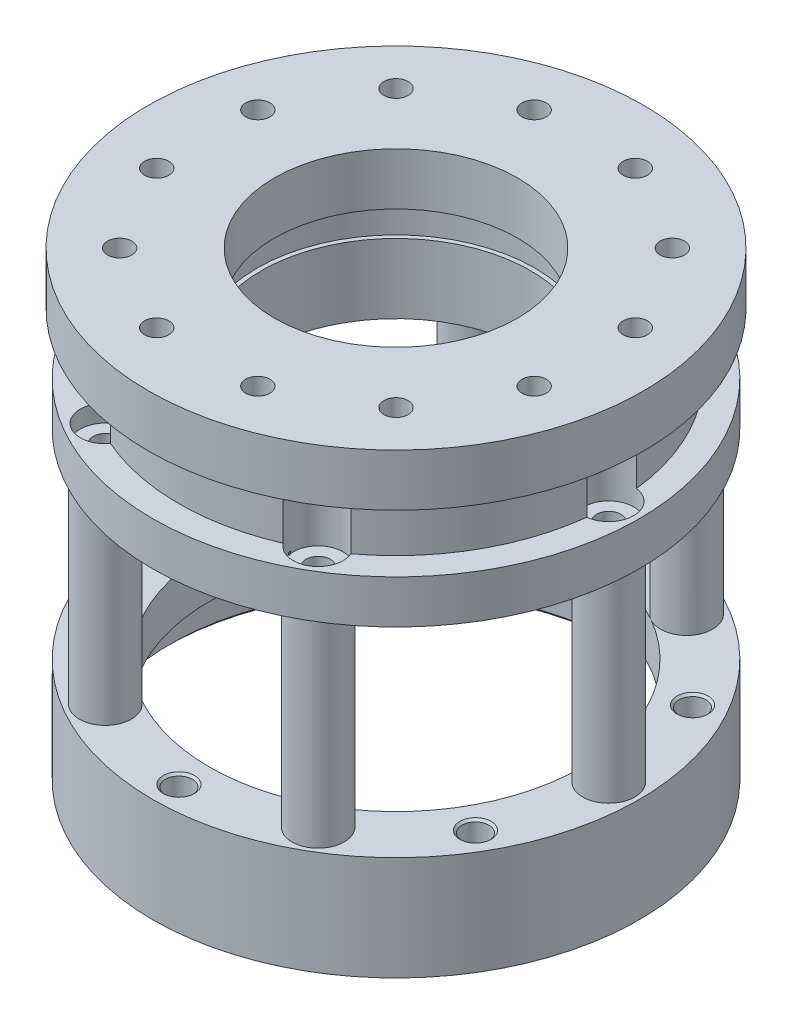
SolidWorks part; units mm, degrees
ref_plane "Front" through (0, 0, 0) normal (0, 0, 1) x (1, 0, 0)
ref_plane "Top" through (0, 0, 0) normal (0, 1, 0) x (1, 0, 0)
ref_plane "Right" through (0, 0, 0) normal (1, 0, 0) x (0, 0, -1)
sketch "Sketch1" plane through (0, 0, 0) normal (0, 1, 0) x (1, 0, 0)
  line L0 (0, 0) -> (24.5, 0) construction
  circle A0 centre (24.5, 0) radius 3
  dimension "D2" = 6
  dimension "D1" = 24.5
extrude "Boss-Extrude1" add sketch "Sketch1" along normal blind 23
ref_axis "Axis1" through (0, -50, 0) along (0, 1, 0)
pattern_circular "CirPattern1" count 6 over 360 about axis through (0, -50, 0) along (0, 1, 0) of "Boss-Extrude1"
sketch "Sketch3" plane through (0, 0, 0) normal (0, 1, 0) x (1, 0, 0)
  circle A0 centre (0, 0) radius 28
  circle A1 centre (0, 0) radius 21.5
  dimension "D1" = 56
  dimension "D2" = 43
extrude "Boss-Extrude2" add sketch "Sketch3" against normal blind 5
sketch "Sketch4" plane through (0, -5, 0) normal (0, -1, 0) x (1, 0, 0)
  circle A0 centre (0, 0) radius 26
  circle A1 centre (0, 0) radius 28 construction
  circle A2 centre (0, 0) radius 28
  dimension "D1" = 52
extrude "Boss-Extrude3" add sketch "Sketch4" along normal blind 7
sketch "Sketch5" plane through (0, 0, 0) normal (0, 1, 0) x (1, 0, 0)
  line L0 (0, 0) -> (21.5, 0) construction
  line L1 (0, 0) -> (21.6506, -12.5) construction
  circle A0 centre (0, 0) radius 21.5 construction
  circle A1 centre (21.6506, -12.5) radius 1.55
  circle A2 centre (0, -25) radius 1.55
  circle A3 centre (-21.6506, -12.5) radius 1.55
  circle A4 centre (-21.6506, 12.5) radius 1.55
  circle A5 centre (0, 25) radius 1.55
  circle A6 centre (21.6506, 12.5) radius 1.55
  dimension "D3" = 3.1
  dimension "D1" = 25
  dimension "D2" = 30
  dimension "D4" = 6
extrude "Cut-Extrude1" cut sketch "Sketch5" against normal blind 4
chamfer "Chamfer1" distance 0.25 angle 45 6 edges at (0, 0, -23.45) (-21.6506, 0, -10.95) (-21.6506, 0, 14.05) (0, 0, 26.55) (21.6506, 0, 14.05) (21.6506, 0, -10.95)
sketch "Sketch6" plane through (0, 23, 0) normal (0, 1, 0) x (1, 0, 0)
  circle A0 centre (0, 0) radius 28
  circle A1 centre (0, 0) radius 15.5
  dimension "D1" = 56
  dimension "D2" = 31
extrude "Boss-Extrude4" add sketch "Sketch6" along normal blind 5 separate body
sketch "Sketch7" plane through (0, 28, 0) normal (0, 1, 0) x (1, 0, 0)
  circle A0 centre (0, 0) radius 25
  circle A1 centre (0, 0) radius 15.5 construction
  circle A2 centre (0, 0) radius 15.5
  dimension "D1" = 50
extrude "Boss-Extrude5" add sketch "Sketch7" along normal blind 7
sketch "Sketch8" plane through (0, 35, 0) normal (0, 1, 0) x (1, 0, 0)
  circle A0 centre (0, 0) radius 16
  dimension "D1" = 32
extrude "Cut-Extrude2" cut sketch "Sketch8" against normal blind 4
sketch "Sketch9" plane through (0, 23, 0) normal (0, -1, 0) x (1, 0, 0)
  circle A0 centre (21.6506, 12.5) radius 1.55 construction
  circle A1 centre (21.6506, 12.5) radius 1.55
extrude "Cut-Extrude3" cut sketch "Sketch9" against normal blind 4.5
chamfer "Chamfer2" distance 0.25 angle 45 1 edges at (21.6506, 23, 10.95)
pattern_circular "CirPattern2" count 6 over 360 about axis through (0, 35, 0) along (0, -1, 0) of "Chamfer2", "Cut-Extrude3"
sketch "Sketch10" plane through (0, 35, 0) normal (0, 1, 0) x (1, 0, 0)
  circle A0 centre (0, 0) radius 28.5
  circle A1 centre (0, 0) radius 14
  dimension "D1" = 57
  dimension "D2" = 28
extrude "Boss-Extrude6" add sketch "Sketch10" along normal blind 6 separate body
sketch "Sketch11" plane through (0, 28, 0) normal (0, 1, 0) x (1, 0, 0)
  circle A0 centre (24.5, 0) radius 2.875
  dimension "D1" = 5.75
extrude "Cut-Extrude4" cut sketch "Sketch11" against normal blind 2 and the other way up to surface (7 mm away) other way up to face at (0, 35, 28.5)
sketch "Sketch12" plane through (0, 26, 0) normal (0, 1, 0) x (1, 0, 0)
  circle A0 centre (24.5, 0) radius 1.4
  dimension "D1" = 2.8
extrude "Cut-Extrude5" cut sketch "Sketch12" against normal blind 28
pattern_circular "CirPattern3" count 6 over 360 about axis through (0, 35, 0) along (0, -1, 0) of "Cut-Extrude4", "Cut-Extrude5" reverse direction yes
chamfer "Chamfer3" distance 0.5 angle 45 1 edges at (0, -12, -26)
sketch "Sketch13" plane through (0, 41, 0) normal (0, 1, 0) x (1, 0, 0)
  line L0 (0, 0) -> (18.4774, 0) construction
  line L1 (0, 0) -> (21.7333, -5.8234) construction
  circle A1 centre (0, 0) radius 16 construction
  circle A2 centre (0, 0) radius 16 construction
  arc A3 (14.8909, -20.0813) -> (24.8364, -2.8552) centre (0, 0) ccw construction
  arc A4 (14.8909, -20.0813) -> (24.8364, -2.8552) centre (0, 0) ccw construction
  circle A5 centre (21.7333, -5.8234) radius 1.4
  circle A6 centre (15.9099, -15.9099) radius 1.4
  circle A7 centre (5.8234, -21.7333) radius 1.4
  circle A8 centre (-5.8234, -21.7333) radius 1.4
  circle A9 centre (-15.9099, -15.9099) radius 1.4
  circle A10 centre (-21.7333, -5.8234) radius 1.4
  circle A11 centre (-21.7333, 5.8234) radius 1.4
  circle A12 centre (-15.9099, 15.9099) radius 1.4
  circle A13 centre (-5.8234, 21.7333) radius 1.4
  circle A14 centre (5.8234, 21.7333) radius 1.4
  circle A15 centre (15.9099, 15.9099) radius 1.4
  circle A16 centre (21.7333, 5.8234) radius 1.4
  dimension "D1" = 2.8
  dimension "D2" = 15
  dimension "D3" = 22.5
  dimension "D4" = 12
extrude "Cut-Extrude6" cut sketch "Sketch13" against normal blind 16
sketch "Sketch14" plane through (0, 23, 0) normal (0, -1, 0) x (1, 0, 0)
  line L0 (0, 0) -> (8.5317, 0) construction
  line L1 (0, 0) -> (21.7333, 5.8234) construction
  line L2 (24.9083, -7.6565) -> (24.9083, -3.9903)
  line L3 (25.3995, 5.8234) -> (23.5664, 8.9984)
  line L4 (23.5664, 8.9984) -> (19.9002, 8.9984)
  line L5 (19.9002, 8.9984) -> (18.0672, 5.8234)
  line L6 (18.0672, 5.8234) -> (19.9002, 2.6484)
  line L7 (19.9002, 2.6484) -> (23.5664, 2.6484)
  line L8 (23.5664, 2.6484) -> (25.3995, 5.8234)
  line L9 (24.9083, -3.9903) -> (21.7333, -2.1573)
  line L10 (21.7333, -2.1573) -> (18.5583, -3.9903)
  line L11 (18.5583, -3.9903) -> (18.5583, -7.6565)
  line L12 (18.5583, -7.6565) -> (21.7333, -9.4896)
  line L13 (21.7333, -9.4896) -> (24.9083, -7.6565)
  line L14 (17.743, -19.0849) -> (19.5761, -15.9099)
  line L15 (19.5761, -15.9099) -> (17.743, -12.7349)
  line L16 (17.743, -12.7349) -> (14.0768, -12.7349)
  line L17 (14.0768, -12.7349) -> (12.2437, -15.9099)
  line L18 (12.2437, -15.9099) -> (14.0768, -19.0849)
  line L19 (14.0768, -19.0849) -> (17.743, -19.0849)
  line L20 (5.8234, -25.3995) -> (8.9984, -23.5664)
  line L21 (8.9984, -23.5664) -> (8.9984, -19.9002)
  line L22 (8.9984, -19.9002) -> (5.8234, -18.0672)
  line L23 (5.8234, -18.0672) -> (2.6484, -19.9002)
  line L24 (2.6484, -19.9002) -> (2.6484, -23.5664)
  line L25 (2.6484, -23.5664) -> (5.8234, -25.3995)
  line L26 (-7.6565, -24.9083) -> (-3.9903, -24.9083)
  line L27 (-3.9903, -24.9083) -> (-2.1573, -21.7333)
  line L28 (-2.1573, -21.7333) -> (-3.9903, -18.5583)
  line L29 (-3.9903, -18.5583) -> (-7.6565, -18.5583)
  line L30 (-7.6565, -18.5583) -> (-9.4896, -21.7333)
  line L31 (-9.4896, -21.7333) -> (-7.6565, -24.9083)
  line L32 (-19.0849, -17.743) -> (-15.9099, -19.5761)
  line L33 (-15.9099, -19.5761) -> (-12.7349, -17.743)
  line L34 (-12.7349, -17.743) -> (-12.7349, -14.0768)
  line L35 (-12.7349, -14.0768) -> (-15.9099, -12.2437)
  line L36 (-15.9099, -12.2437) -> (-19.0849, -14.0768)
  line L37 (-19.0849, -14.0768) -> (-19.0849, -17.743)
  line L38 (-25.3995, -5.8234) -> (-23.5664, -8.9984)
  line L39 (-23.5664, -8.9984) -> (-19.9002, -8.9984)
  line L40 (-19.9002, -8.9984) -> (-18.0672, -5.8234)
  line L41 (-18.0672, -5.8234) -> (-19.9002, -2.6484)
  line L42 (-19.9002, -2.6484) -> (-23.5664, -2.6484)
  line L43 (-23.5664, -2.6484) -> (-25.3995, -5.8234)
  line L44 (-24.9083, 7.6565) -> (-24.9083, 3.9903)
  line L45 (-24.9083, 3.9903) -> (-21.7333, 2.1573)
  line L46 (-21.7333, 2.1573) -> (-18.5583, 3.9903)
  line L47 (-18.5583, 3.9903) -> (-18.5583, 7.6565)
  line L48 (-18.5583, 7.6565) -> (-21.7333, 9.4896)
  line L49 (-21.7333, 9.4896) -> (-24.9083, 7.6565)
  line L50 (-17.743, 19.0849) -> (-19.5761, 15.9099)
  line L51 (-19.5761, 15.9099) -> (-17.743, 12.7349)
  line L52 (-17.743, 12.7349) -> (-14.0768, 12.7349)
  line L53 (-14.0768, 12.7349) -> (-12.2437, 15.9099)
  line L54 (-12.2437, 15.9099) -> (-14.0768, 19.0849)
  line L55 (-14.0768, 19.0849) -> (-17.743, 19.0849)
  line L56 (-5.8234, 25.3995) -> (-8.9984, 23.5664)
  line L57 (-8.9984, 23.5664) -> (-8.9984, 19.9002)
  line L58 (-8.9984, 19.9002) -> (-5.8234, 18.0672)
  line L59 (-5.8234, 18.0672) -> (-2.6484, 19.9002)
  line L60 (-2.6484, 19.9002) -> (-2.6484, 23.5664)
  line L61 (-2.6484, 23.5664) -> (-5.8234, 25.3995)
  line L62 (7.6565, 24.9083) -> (3.9903, 24.9083)
  line L63 (3.9903, 24.9083) -> (2.1573, 21.7333)
  line L64 (2.1573, 21.7333) -> (3.9903, 18.5583)
  line L65 (3.9903, 18.5583) -> (7.6565, 18.5583)
  line L66 (7.6565, 18.5583) -> (9.4896, 21.7333)
  line L67 (9.4896, 21.7333) -> (7.6565, 24.9083)
  line L68 (19.0849, 17.743) -> (15.9099, 19.5761)
  line L69 (15.9099, 19.5761) -> (12.7349, 17.743)
  line L70 (12.7349, 17.743) -> (12.7349, 14.0768)
  line L71 (12.7349, 14.0768) -> (15.9099, 12.2437)
  line L72 (15.9099, 12.2437) -> (19.0849, 14.0768)
  line L73 (19.0849, 14.0768) -> (19.0849, 17.743)
  circle A0 centre (21.7333, 5.8234) radius 3.175 construction
  circle A1 centre (21.7333, -5.8234) radius 3.175 construction
  circle A2 centre (15.9099, -15.9099) radius 3.175 construction
  circle A3 centre (5.8234, -21.7333) radius 3.175 construction
  circle A4 centre (-5.8234, -21.7333) radius 3.175 construction
  circle A5 centre (-15.9099, -15.9099) radius 3.175 construction
  circle A6 centre (-21.7333, -5.8234) radius 3.175 construction
  circle A7 centre (-21.7333, 5.8234) radius 3.175 construction
  circle A8 centre (-15.9099, 15.9099) radius 3.175 construction
  circle A9 centre (-5.8234, 21.7333) radius 3.175 construction
  circle A10 centre (5.8234, 21.7333) radius 3.175 construction
  circle A11 centre (15.9099, 15.9099) radius 3.175 construction
  dimension "D1" = 15
  dimension "D2" = 22.5
  dimension "D3" = 6.35
  dimension "D4" = 12
extrude "Cut-Extrude7" cut sketch "Sketch14" against normal blind 3.25
chamfer "Chamfer4" distance 0.5 angle 45 7 edges at (0, 35, 16) (0, 35, 25) (21.6506, 35, 12.5) (21.6506, 35, -12.5) (0, 35, -25) (-21.6506, 35, -12.5) (-21.6506, 35, 12.5)
sketch "Sketch15" [suppressed] plane through (0, 41, 0) normal (0, 1, 0) x (1, 0, 0)
  line L0 (0, 0) -> (200, 0) construction
  line L1 (2.3571, 28.4024) -> (200, 12)
  line L2 (200, -12) -> (2.3571, -28.4024)
  circle A0 centre (0, 0) radius 17.3405
  arc A1 (2.3571, 28.4024) -> (2.3571, -28.4024) centre (0, 0) ccw
  arc A2 (200, -12) -> (200, 12) centre (200, 0) ccw
  circle A3 centre (0, 0) radius 28.5 construction
  dimension "D1" = 200
  dimension "D2" = 24
extrude "Boss-Extrude7" [suppressed] add sketch "Sketch15" along normal blind 6 separate body
sketch "Sketch16" [suppressed] plane through (0, 47, 0) normal (0, 1, 0) x (1, 0, 0)
  circle A0 centre (200, 0) radius 6
  dimension "D1" = 12
extrude "Boss-Extrude8" [suppressed] add sketch "Sketch16" along normal blind 14
sketch "Sketch17" [suppressed] plane through (0, 61, 0) normal (0, 1, 0) x (1, 0, 0)
  circle A0 centre (200, 0) radius 10
  dimension "D1" = 20
extrude "Boss-Extrude9" [suppressed] add sketch "Sketch17" along normal blind 4
sketch "Sketch18" [suppressed] plane through (0, 47, 0) normal (0, 1, 0) x (1, 0, 0)
  circle A0 centre (52.1814, 0) radius 14.0548
  circle A1 centre (88.1102, 0) radius 8.9972
  circle A2 centre (119.7664, 0) radius 7.2286
  circle A3 centre (149.4804, 0) radius 5.4975
extrude "Cut-Extrude8" [suppressed] cut sketch "Sketch18" against normal through all
sketch "Sketch20" [suppressed] plane through (0, 47, 0) normal (0, 1, 0) x (1, 0, 0)
  circle A0 centre (21.7333, 5.8234) radius 1.4 construction
  circle A1 centre (21.7333, -5.8234) radius 1.4 construction
  circle A2 centre (21.7333, 5.8234) radius 1.4
  circle A3 centre (21.7333, -5.8234) radius 1.4
  circle A4 centre (15.9099, -15.9099) radius 1.4 construction
  circle A5 centre (5.8234, -21.7333) radius 1.4 construction
  circle A6 centre (-5.8234, -21.7333) radius 1.4 construction
  circle A7 centre (-15.9099, -15.9099) radius 1.4 construction
  circle A8 centre (-21.7333, -5.8234) radius 1.4 construction
  circle A9 centre (-21.7333, 5.8234) radius 1.4 construction
  circle A10 centre (-15.9099, 15.9099) radius 1.4 construction
  circle A11 centre (-5.8234, 21.7333) radius 1.4 construction
  circle A12 centre (5.8234, 21.7333) radius 1.4 construction
  circle A13 centre (15.9099, 15.9099) radius 1.4 construction
  circle A14 centre (15.9099, -15.9099) radius 1.4
  circle A15 centre (5.8234, -21.7333) radius 1.4
  circle A16 centre (-5.8234, -21.7333) radius 1.4
  circle A17 centre (-15.9099, -15.9099) radius 1.4
  circle A18 centre (-21.7333, -5.8234) radius 1.4
  circle A19 centre (-21.7333, 5.8234) radius 1.4
  circle A20 centre (-15.9099, 15.9099) radius 1.4
  circle A21 centre (-5.8234, 21.7333) radius 1.4
  circle A22 centre (5.8234, 21.7333) radius 1.4
  circle A23 centre (15.9099, 15.9099) radius 1.4
extrude "Cut-Extrude9" [suppressed] cut sketch "Sketch20" against normal up to surface (6 mm away) up to face at (21.7333, 41, 7.2234)
sketch "Sketch21" [suppressed] plane through (0, 35, 0) normal (0, -1, 0) x (1, 0, 0)
  circle A0 centre (0, 0) radius 16
  dimension "D1" = 32
extrude "Cut-Extrude10" [suppressed] cut sketch "Sketch21" against normal blind 1
sketch "Sketch22" [suppressed] plane through (0, -4, 0) normal (0, 1, 0) x (1, 0, 0)
  circle A1 centre (21.6506, -12.5) radius 1.55
  circle A2 centre (21.6506, -12.5) radius 1.55
  dimension "D1" = 0
extrude "Boss-Extrude10" [suppressed] add sketch "Sketch22" along normal up to surface (31.5 mm away) separate body up to face at (21.6506, 27.5, 10.95)
pattern_circular "CirPattern5" [suppressed] count 6 over 360 reverse direction yes of bodies 133
sketch "Sketch23" [suppressed] plane through (0, 23, 0) normal (0, 1, 0) x (1, 0, 0)
  circle A0 centre (12.25, -21.2176) radius 1.4 construction
  circle A1 centre (12.25, -21.2176) radius 3
  circle A2 centre (12.25, -21.2176) radius 3
  circle A3 centre (12.25, -21.2176) radius 1.4
  dimension "D1" = 0
extrude "Boss-Extrude11" [suppressed] add sketch "Sketch23" along normal blind 2 separate body
sketch "Sketch24" [suppressed] plane through (0, 41, 0) normal (0, 1, 0) x (1, 0, 0)
  line L0 (0, 0) -> (200, 0) construction
  line L1 (3.0625, 34.8658) -> (201.5313, 17.4329)
  line L2 (3.0625, -34.8658) -> (201.5313, -17.4329)
  circle A4 centre (0, 0) radius 14 construction
  circle A5 centre (0, 0) radius 14
  arc A6 (3.0625, 34.8658) -> (3.0625, -34.8658) centre (0, 0) ccw
  arc A7 (201.5313, -17.4329) -> (201.5313, 17.4329) centre (200, 0) ccw
  arc A8 (35, 0) -> (3.0625, 34.8658) centre (0, 0) ccw construction
  arc A9 (3.0625, -34.8658) -> (35, 0) centre (0, 0) ccw construction
  arc A10 (182.5, 0) -> (201.5313, -17.4329) centre (200, 0) ccw construction
  arc A11 (201.5313, 17.4329) -> (182.5, 0) centre (200, 0) ccw construction
  dimension "D2" = 70
  dimension "D3" = 35
  dimension "D1" = 200
extrude "Boss-Extrude12" [suppressed] add sketch "Sketch24" along normal blind 20 separate body
sketch "Sketch25" [suppressed] plane through (0, 61, 0) normal (0, 1, 0) x (1, 0, 0)
  line L0 (0, 0) -> (200, 0) construction
  line L1 (200, 0) -> (210, 0) construction
  circle A0 centre (59.8852, 0) radius 20.3471
  circle A1 centre (116.238, 0) radius 16.1539
  circle A2 centre (164.0017, 0) radius 10.0532
  circle A3 centre (210, 0) radius 1.4
  circle A4 centre (203.0902, -9.5106) radius 1.4
  circle A5 centre (191.9098, -5.8779) radius 1.4
  circle A6 centre (191.9098, 5.8779) radius 1.4
  circle A7 centre (203.0902, 9.5106) radius 1.4
  dimension "D3" = 2.8
  dimension "D1" = 200
  dimension "D2" = 10
  dimension "D4" = 5
extrude "Cut-Extrude11" [suppressed] cut sketch "Sketch25" against normal up to surface (20 mm away) up to face at (21.7333, 41, 7.2234)
sketch "Sketch27" [suppressed] plane through (0, 61, 0) normal (0, 1, 0) x (1, 0, 0)
  circle A3 centre (21.7333, 5.8234) radius 1.4
  circle A4 centre (21.7333, 5.8234) radius 1.4
  circle A5 centre (15.9099, 15.9099) radius 1.4
  circle A6 centre (15.9099, 15.9099) radius 1.4
  circle A7 centre (5.8234, 21.7333) radius 1.4
  circle A8 centre (5.8234, 21.7333) radius 1.4
  circle A9 centre (-5.8234, 21.7333) radius 1.4
  circle A10 centre (-5.8234, 21.7333) radius 1.4
  circle A11 centre (-15.9099, 15.9099) radius 1.4
  circle A12 centre (-15.9099, 15.9099) radius 1.4
  circle A13 centre (-21.7333, 5.8234) radius 1.4
  circle A14 centre (-21.7333, 5.8234) radius 1.4
  circle A15 centre (-21.7333, -5.8234) radius 1.4
  circle A16 centre (-21.7333, -5.8234) radius 1.4
  circle A17 centre (-15.9099, -15.9099) radius 1.4
  circle A18 centre (-15.9099, -15.9099) radius 1.4
  circle A19 centre (-5.8234, -21.7333) radius 1.4
  circle A20 centre (-5.8234, -21.7333) radius 1.4
  circle A21 centre (5.8234, -21.7333) radius 1.4
  circle A22 centre (5.8234, -21.7333) radius 1.4
  circle A23 centre (15.9099, -15.9099) radius 1.4
  circle A24 centre (15.9099, -15.9099) radius 1.4
  circle A25 centre (21.7333, -5.8234) radius 1.4
  circle A26 centre (21.7333, -5.8234) radius 1.4
  dimension "D2" = 0
  dimension "D3" = 0
  dimension "D4" = 0
  dimension "D5" = 0
  dimension "D6" = 0
  dimension "D7" = 0
  dimension "D8" = 0
  dimension "D9" = 0
  dimension "D10" = 0
  dimension "D11" = 0
  dimension "D12" = 0
  dimension "D13" = 0
extrude "Cut-Extrude12" [suppressed] cut sketch "Sketch27" against normal up to surface (20 mm away) up to face at (21.7333, 41, 7.2234)
fillet "Fillet1" [suppressed] radius 5
